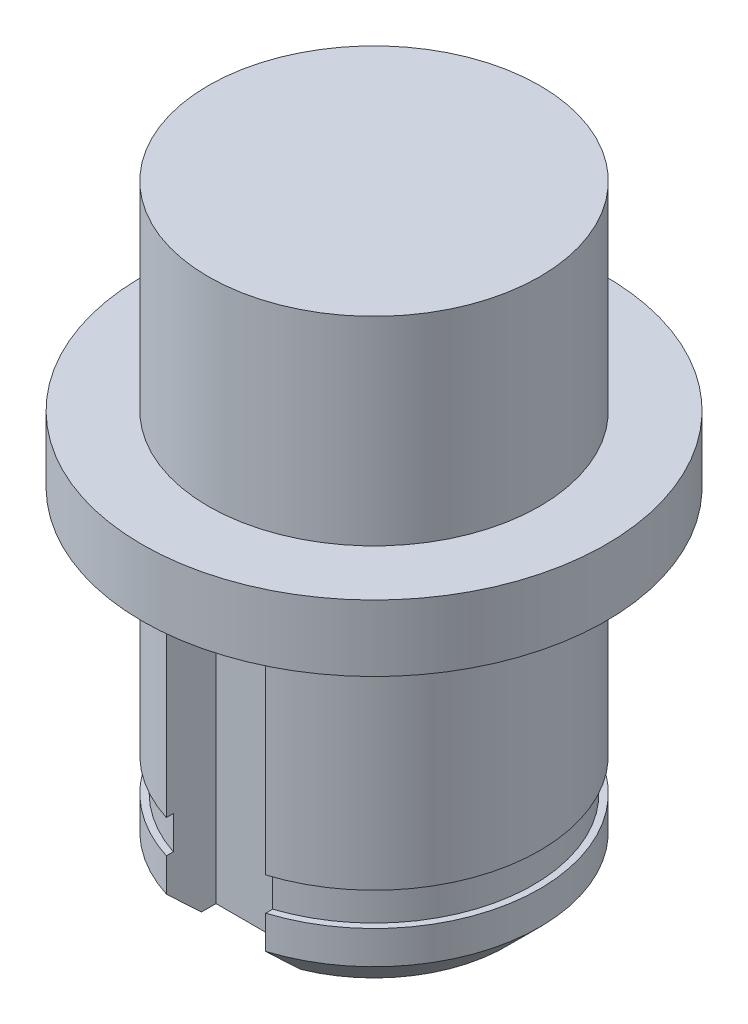
SolidWorks part; units mm, degrees
material "Nylon 101"
ref_plane "Front Plane" through (0, 0, 0) normal (0, 0, 1) x (1, 0, 0)
ref_plane "Top Plane" through (0, 0, 0) normal (0, 1, 0) x (1, 0, 0)
ref_plane "Right Plane" through (0, 0, 0) normal (1, 0, 0) x (0, 0, -1)
sketch "Sketch1" plane through (0, 0, 0) normal (0, 1, 0) x (1, 0, 0)
  circle A0 centre (0, 0) radius 5
  dimension "D1" = 10
extrude "Boss-Extrude1" add sketch "Sketch1" along normal blind 18
ref_axis "Axis1" through (0, 18, 0) along (0, -1, 0)
sketch "Sketch2" plane through (0, 0, 0) normal (1, 0, 0) x (0, 0, -1)
  line L0 (5, 0) -> (5, 18) construction
  line L1 (4.8, 3) -> (5, 3)
  line L2 (4.8, 3) -> (4.8, 2)
  line L3 (4.8, 2) -> (5, 2)
  line L4 (5, 3) -> (5, 2)
  line L5 (5, 18) -> (-5, 18) construction
  line L6 (5, 12) -> (7, 12)
  line L7 (5, 12) -> (5, 10)
  line L8 (5, 10) -> (7, 10)
  line L9 (7, 12) -> (7, 10)
  dimension "D1" = 7
  dimension "D2" = 2
  dimension "D3" = 6
  dimension "D4" = 1
  dimension "D5" = 4.8
  dimension "D6" = 7
revolve "Revolve1" add sketch "Sketch2" angle 360 about axis through (0, 18, 0) along (0, -1, 0) region at (0, 11, -6)
revolve "Cut-Revolve1" cut sketch "Sketch2<5>" angle 360 about axis through (0, 18, 0) along (0, -1, 0) region at (0, 2.5, -4.9)
sketch "Sketch2<5>" plane through (0, 0, 0) normal (1, 0, 0) x (0, 0, -1) same geometry as "Sketch2"
sketch "Sketch4" plane through (0, 0, 0) normal (0, -1, 0) x (1, 0, 0)
  line L0 (0, 0) -> (0, 7.4336) construction
  line L2 (-1.5, 4.7697) -> (-1.5, 3.2697)
  line L3 (-1.5, 3.2697) -> (1.5, 3.2697)
  line L4 (1.5, 4.7697) -> (1.5, 3.2697)
  circle A0 centre (0, 0) radius 5 construction
  dimension "D1" = 1.5
  dimension "D2" = 3
extrude "Cut-Extrude1" cut sketch "Sketch4" against normal blind 10 and the other way through all flip side to cut
sketch "Sketch5" plane through (0, 0, 0) normal (0, -1, 0) x (1, 0, 0)
  line L0 (1.5, 2) -> (-1.5, 2)
  arc A0 (-1.5, 2) -> (1.5, 2) centre (0, 0) ccw
  dimension "D1" = 5
  dimension "D2" = 3
extrude "Cut-Extrude2" cut sketch "Sketch5" against normal blind 16
chamfer "Chamfer2" distance 1 angle 45 1 edges at (0, 0, -5)
